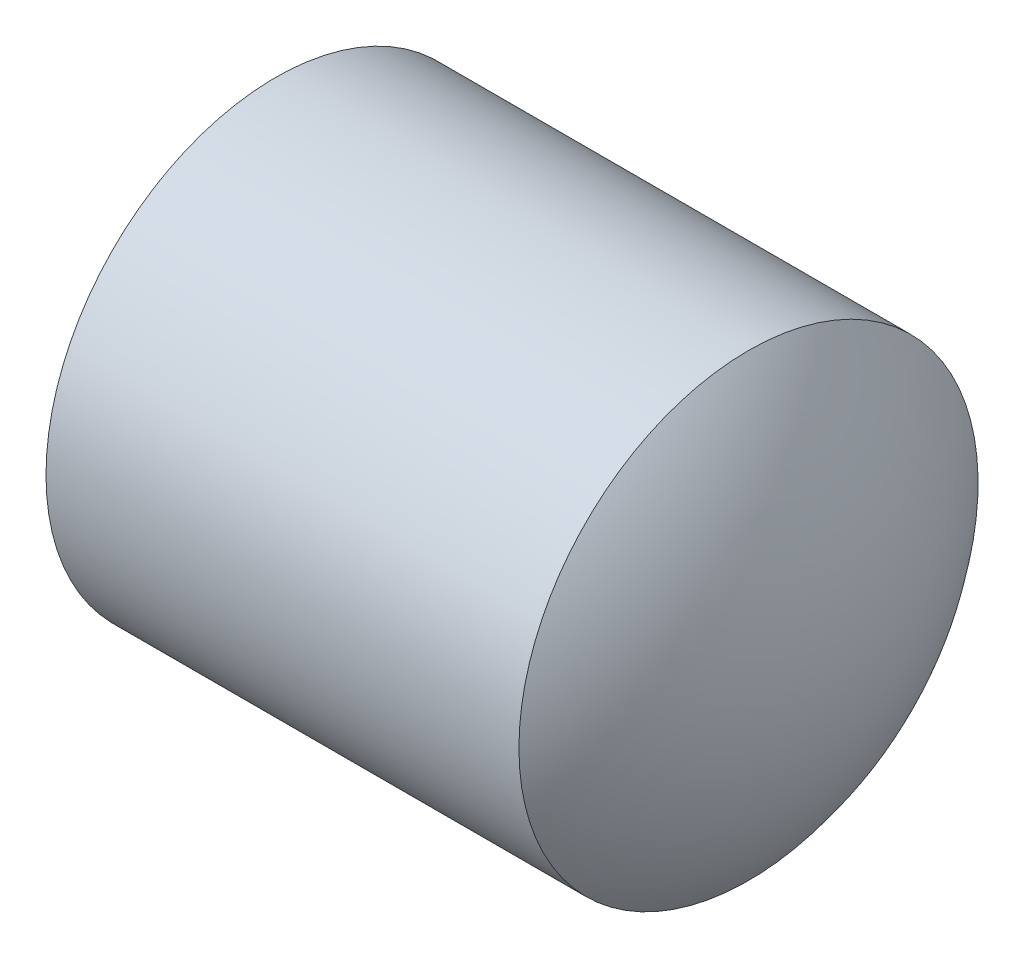
SolidWorks part; units mm, degrees
revolve "BaseBody" add sketch "BodySke" angle 360 about L5 other way angle 60
sketch "BodySke" plane through (0, 0, 0) normal (0, 0, 1) x (1, 0, 0)
  line L0 (0, 0) -> (0, 10.352)
  line L1 (0, 10.352) -> (0.9515, 12)
  line L2 (0.9515, 12) -> (25.672, 12)
  line L3 (3, 15.875) -> (3, -3.175) construction
  line L4 (30, 0) -> (0, 0)
  line L5 (-12.7, 0) -> (88.9, 0) construction
  line L8 (0, -10.352) -> (0.9515, -12) construction
  arc A0 (30, 0) -> (25.672, 12) centre (11.2, 0) ccw
  dimension "Length" = 30
  dimension "Diameter" = 24
cosmetic thread "ThreadCosmetic" [suppressed] parameters "Thread_minor"=20.704
ref_plane "Plane1" through (0, 0, 0) normal (0, 0, 1) x (1, 0, 0)
ref_plane "Plane2" through (0, 0, 0) normal (0, 1, 0) x (1, 0, 0)
ref_plane "Plane3" through (0, 0, 0) normal (1, 0, 0) x (0, 0, -1)
sketch "Sketch2" plane through (0, 0, 0) normal (-1, 0, 0) x (0, 0, 1)
  line L0 (3.4641, 6) -> (-3.4641, 6)
  line L1 (-3.4641, 6) -> (-6.9282, 0)
  line L2 (3.4641, 6) -> (6.9282, 0)
  line L3 (3.4641, -6) -> (6.9282, 0)
  line L4 (3.4641, -6) -> (-3.4641, -6)
  line L5 (-3.4641, -6) -> (-6.9282, 0)
  dimension "D2" = 6
  dimension "D3" = 6
extrude "Hex" cut sketch "Sketch2" against normal blind 12
sketch "Sketch4" plane through (0, 4.7709, -0.5249) normal (-1, 0, 0) x (0, 0, 1)
  line L0 (0.5249, -4.7709) -> (10.6976, -4.7709)
  line L1 (0.5249, -4.7709) -> (6.6732, -1.2211) construction
  line L2 (0.5249, -4.7709) -> (5.6112, 4.0389)
  line L3 (8.9666, -2.6687) -> (10.2861, -1.9069)
  line L4 (6.5663, 1.4888) -> (7.8858, 2.2506)
  arc A0 (8.9666, -2.6687) -> (6.5663, 1.4888) centre (0.5249, -4.7709) ccw
  arc A1 (10.6976, -4.7709) -> (10.2861, -1.9069) centre (0.5249, -4.7709) ccw
  arc A2 (5.6112, 4.0389) -> (7.8858, 2.2506) centre (0.5249, -4.7709) cw
  circle A3 centre (0.5249, -4.7709) radius 8.6995 construction
  circle A4 centre (0.5249, -4.7709) radius 10.1727 construction
  dimension "Spline_n_dim" = 17.399
  dimension "Spline_m_dim" = 20.3454
  dimension "D1" = 30
  dimension "Spline_p_dim" = 4.8006
  dimension "D3" = 2.4003
extrude "Spline6" [suppressed] cut sketch "Sketch4" against normal blind 12
pattern_circular "CirPattern1" [suppressed] count 6 every 60 about axis through (-12.7, 0, 0) along (1, 0, 0)
sketch "Sketch5" plane through (0, -2.3417, -0.7053) normal (-1, 0, 0) x (0, 0, 1)
  line L0 (0.7053, 2.3417) -> (10.878, 2.3417)
  line L1 (0.7053, 2.3417) -> (5.7254, 7.3618) construction
  line L2 (0.7053, 2.3417) -> (0.7053, 12.5144)
  line L3 (8.554, 6.7959) -> (9.3926, 7.6345)
  line L4 (5.1595, 10.1904) -> (5.9981, 11.029)
  line L5 (5.1595, 10.1904) -> (8.554, 6.7959)
  arc A1 (10.878, 2.3417) -> (9.3926, 7.6345) centre (0.7053, 2.3417) ccw
  arc A2 (0.7053, 12.5144) -> (5.9981, 11.029) centre (0.7053, 2.3417) cw
  circle A3 centre (0.7053, 2.3417) radius 8.6995 construction
  circle A4 centre (0.7053, 2.3417) radius 10.1727 construction
  dimension "Spline_n_dim" = 17.399
  dimension "Spline_m_dim" = 20.3454
  dimension "Spline_p_dim" = 4.8006
  dimension "D3" = 2.4003
  dimension "D1" = 45
  dimension "Spline_a_dim" = 90
extrude "Spline4" [suppressed] cut sketch "Sketch5" against normal blind 12
pattern_circular "CirPattern2" [suppressed] count 4 every 90 about axis through (-12.7, 0, 0) along (1, 0, 0)
sketch "ThdSchSke" plane through (0, 0, 0) normal (0, 0, 1) x (1, 0, 0)
  line L0 (0.9515, -10.352) -> (-0.2025, -12)
  line L1 (0.9515, -10.352) -> (2.1054, -12)
  line L2 (2.1054, -12) -> (2.1054, -15)
  line L3 (-3.175, 0) -> (5.1513, 0) construction
  line L4 (0.9515, 12) -> (0.9515, -12) construction
  line L5 (2.1054, -15) -> (-0.2025, -15)
  line L6 (-0.2025, -15) -> (-0.2025, -12)
  dimension "Thread_minor" = 20.704
  dimension "Diameter" = 24
revolve "ThreadSchematic" [suppressed] cut sketch "ThdSchSke" angle 360 about L3
pattern_linear "ThdSchPat" [suppressed]
equation "\"D2@Sketch2\" = \"Hex_size@Sketch2\" / 2"
equation "\"D3@Sketch2\" = \"Hex_size@Sketch2\" / 2"
equation "\"Thread_minor@ThreadCosmetic\" = \"Minor_dia@BodySke\""
equation "\"D1@Sketch4\" = \"Spline_a_dim@Sketch4\" / 2"
equation "\"D3@Sketch4\" = \"Spline_p_dim@Sketch4\" / 2"
equation "\"D2@CirPattern1\" = \"Spline_a_dim@Sketch4\""
equation "\"Num_teeth@CirPattern1\" = 360 / \"D2@CirPattern1\""
equation "\"Spline_a_dim@Sketch5\" = 90"
equation "\"Spline_p_dim@Sketch5\" = \"Spline_p_dim@Sketch4\""
equation "\"Spline_m_dim@Sketch5\" = \"Spline_m_dim@Sketch4\""
equation "\"Spline_n_dim@Sketch5\" = \"Spline_n_dim@Sketch4\""
equation "\"D1@Sketch5\" = \"Spline_a_dim@Sketch5\" / 2"
equation "\"D3@Sketch5\" = \"Spline_p_dim@Sketch5\" / 2"
equation "\"Key_eng@Spline4\" = \"Key_eng@Spline6\""
equation "\"Thread_minor@ThdSchSke\" = \"Thread_minor@ThreadCosmetic\""
equation "\"Diameter@ThdSchSke\" = \"Diameter@BodySke\""
equation "\"Overcut@ThdSchSke\" = \"Diameter@BodySke\" * 1.25"
equation "\"Num_threads@ThdSchPat\" = int( (\"Length@BodySke\" - ( ( ( \"Diameter@BodySke\" - \"Minor_dia@BodySke\" ) * 0.5 ) / tan( \"Drive_ch_ang@BodySke\" * 0.017453292 ) ) - ( \"Oval_radius@BodySke\" - sqr ( ( \"Oval_radius@BodySke\" * \"Oval_radius@BodySke\" ) - ( ( \"Diameter@BodySke\" * 0.5 ) * ( \"Diameter@BodySke\" * 0.5 ) ) ) ) ) / \"Advance@BodySke\" + 0.999 )  + 1"
equation "\"Advance@ThdSchPat\" = (\"Length@BodySke\" - ( ( ( \"Diameter@BodySke\" - \"Minor_dia@BodySke\" ) * 0.5 ) / tan( \"Drive_ch_ang@BodySke\" * 0.017453292 ) ) - ( \"Oval_radius@BodySke\" - sqr ( ( \"Oval_radius@BodySke\" * \"Oval_radius@BodySke\" ) - ( ( \"Diameter@BodySke\" * 0.5 ) * ( \"Diameter@BodySke\" * 0.5 ) ) ) ) ) /  (\"Num_threads@ThdSchPat\" - 1) 'relax it"
equation "' \"Num_threads@ThdSchPat\" = \"Num_threads@ThdSchPat\" - sgn( \"Num_threads@ThdSchPat\" - 1) '---chamfered tips only---"
